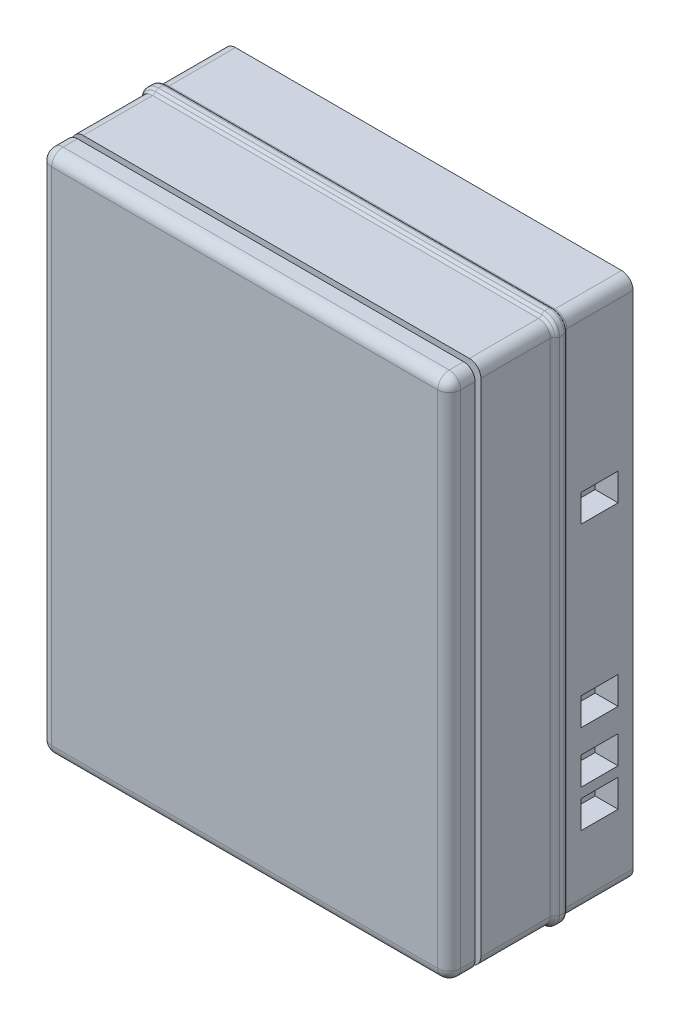
SolidWorks part; units mm, degrees
ref_plane "Alzado" through (0, 0, 0) normal (0, 0, 1) x (1, 0, 0)
ref_plane "Planta" through (0, 0, 0) normal (0, 1, 0) x (1, 0, 0)
ref_plane "Vista lateral" through (0, 0, 0) normal (1, 0, 0) x (0, 0, -1)
sketch "Croquis1" plane through (0, 0, 0) normal (0, 0, 1) x (1, 0, 0)
  line L1 (-178, -228) -> (178, -228)
  line L2 (-178, -228) -> (-178, 228)
  line L3 (-178, 228) -> (178, 228)
  line L4 (178, -228) -> (178, 228)
  line L5 (-178, -228) -> (178, 228) construction
  line L6 (-178, 228) -> (178, -228) construction
  point P0 (0, 0)
  point P6 (0, 0)
  dimension "D1" = 356
  dimension "D2" = 456
extrude "Saliente-Extruir1" add sketch "Croquis1" along normal blind 160
ref_plane "Plano1" through (0, 0, 135) normal (0, 0, 1) x (1, 0, 0)
fillet "Redondeo1" radius 10 8 edges at (-178, -228, 80) (-178, 228, 80) (0, -228, 160) (178, -228, 80) (178, 228, 80) (-178, 0, 160) (178, 0, 160) (0, 228, 160)
sketch "Croquis2" plane through (0, 0, 160) normal (0, 0, 1) x (1, 0, 0)
  line L1 (-178, -228) -> (178, -228)
  line L2 (-178, -228) -> (-178, 228)
  line L3 (-178, 228) -> (178, 228)
  line L4 (178, -228) -> (178, 228)
  line L5 (-178, -228) -> (178, 228) construction
  line L6 (-178, 228) -> (178, -228) construction
  line L7 (-168, -218) -> (168, -218)
  line L8 (-168, -218) -> (-168, 218)
  line L9 (-168, 218) -> (168, 218)
  line L10 (168, -218) -> (168, 218)
  line L11 (-168, -218) -> (168, 218) construction
  line L12 (-168, 218) -> (168, -218) construction
  point P0 (0, 0)
  point P6 (0, 0)
extrude "Cortar-Extruir1" cut sketch "Croquis2" against normal blind 2.5 and the other way blind 2.5 from surface starting at plane "Plano1"
fillet "Redondeo2" radius 10 4 edges at (-168, -218, 135) (168, -218, 135) (168, 218, 135) (-168, 218, 135)
ref_plane "Plano2" through (0, 0, 65) normal (0, 0, 1) x (1, 0, 0)
sketch "Croquis4" plane through (0, 0, 65) normal (0, 0, 1) x (1, 0, 0)
  line L1 (168, -231) -> (-168, -231)
  line L2 (181, -218) -> (181, 218)
  line L3 (168, 231) -> (-168, 231)
  line L4 (-181, -218) -> (-181, 218)
  line L5 (177.6442, -226.7172) -> (-177.6442, 226.7172) construction
  line L6 (177.6442, 226.7172) -> (-177.6442, -226.7172) construction
  arc A0 (-181, 218) -> (-168, 231) centre (-168, 218) cw
  arc A1 (-168, -231) -> (-181, -218) centre (-168, -218) cw
  arc A2 (168, -231) -> (181, -218) centre (168, -218) ccw
  arc A3 (181, 218) -> (168, 231) centre (168, 218) ccw
  point P0 (0, 0)
extrude "Saliente-Extruir2" add sketch "Croquis4" along normal blind 5 and the other way blind 5
fillet "Redondeo6" radius 3 16 edges at (181, 0, 70) (181, 0, 60) (0, 231, 60) (0, 231, 70) (-181, 0, 60) (-181, 0, 70) (0, -231, 60) (0, -231, 70) (-177.1924, -227.1924, 60) (-177.1924, 227.1924, 60) (177.1924, 227.1924, 60) (177.1924, -227.1924, 60) (-177.1924, -227.1924, 70) (-177.1924, 227.1924, 70) (177.1924, 227.1924, 70) (177.1924, -227.1924, 70)
fillet "Redondeo7" radius 3 8 edges at (175.0711, -225.0711, 60) (178, 0, 60) (175.0711, 225.0711, 60) (0, 228, 60) (-175.0711, 225.0711, 60) (-178, 0, 60) (-175.0711, -225.0711, 60) (0, -228, 60)
fillet "Redondeo8" radius 3 8 edges at (175.0711, -225.0711, 70) (178, 0, 70) (175.0711, 225.0711, 70) (0, 228, 70) (-175.0711, 225.0711, 70) (-178, 0, 70) (-175.0711, -225.0711, 70) (0, -228, 70)
sketch "Croquis5" plane through (178, 0, 0) normal (1, 0, 0) x (0, 0, -1)
  line L1 (-45.5538, -166.5225) -> (-13.0538, -166.5225)
  line L2 (-45.5538, -166.5225) -> (-45.5538, -142.3225)
  line L3 (-45.5538, -142.3225) -> (-13.0538, -142.3225)
  line L4 (-13.0538, -166.5225) -> (-13.0538, -142.3225)
  line L5 (-45.5538, -166.5225) -> (-13.0538, -142.3225) construction
  line L6 (-45.5538, -142.3225) -> (-13.0538, -166.5225) construction
  line L7 (-45.5538, -133.7448) -> (-13.0538, -133.7448)
  line L8 (-45.5538, -133.7448) -> (-45.5538, -109.4688)
  line L9 (-45.5538, -109.4688) -> (-13.0538, -109.4688)
  line L10 (-13.0538, -133.7448) -> (-13.0538, -109.4688)
  line L11 (-45.5538, -133.7448) -> (-13.0538, -109.4688) construction
  line L12 (-45.5538, -109.4688) -> (-13.0538, -133.7448) construction
  line L13 (-45.5538, -88.9572) -> (-13.0538, -88.9572)
  line L14 (-45.5538, -88.9572) -> (-45.5538, -64.8577)
  line L15 (-45.5538, -64.8577) -> (-13.0538, -64.8577)
  line L16 (-13.0538, -88.9572) -> (-13.0538, -64.8577)
  line L17 (-45.5538, -88.9572) -> (-13.0538, -64.8577) construction
  line L18 (-45.5538, -64.8577) -> (-13.0538, -88.9572) construction
  line L19 (-45.5538, 64.4326) -> (-13.0538, 64.4326)
  line L20 (-45.5538, 64.4326) -> (-45.5538, 88.3989)
  line L21 (-45.5538, 88.3989) -> (-13.0538, 88.3989)
  line L22 (-13.0538, 64.4326) -> (-13.0538, 88.3989)
  line L23 (-45.5538, 64.4326) -> (-13.0538, 88.3989) construction
  line L24 (-45.5538, 88.3989) -> (-13.0538, 64.4326) construction
  point P0 (-29.3038, -154.4225)
  point P6 (-29.3038, -121.6068)
  point P12 (-29.3038, -76.9075)
  point P18 (-29.3038, 76.4158)
extrude "Cortar-Extruir2" cut sketch "Croquis5" against normal blind 20
